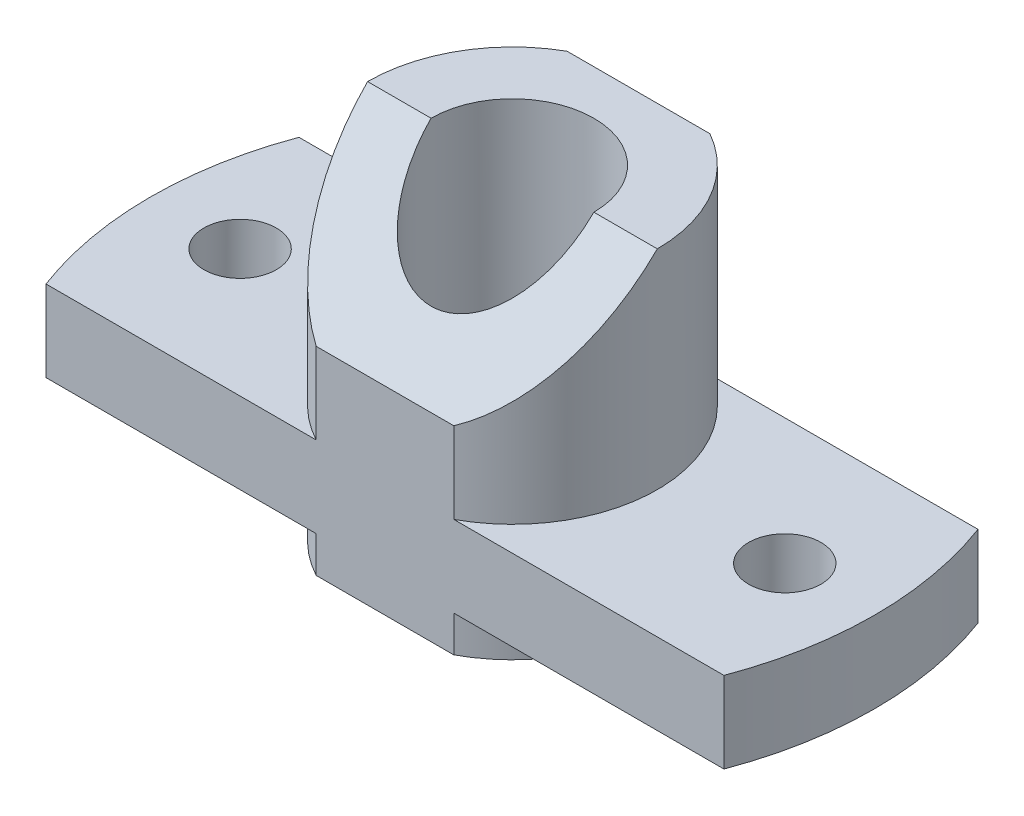
SolidWorks part; units mm, degrees
ref_plane "Front Plane" through (0, 0, 0) normal (0, 0, 1) x (1, 0, 0)
ref_plane "Top Plane" through (0, 0, 0) normal (0, 1, 0) x (1, 0, 0)
ref_plane "Right Plane" through (0, 0, 0) normal (1, 0, 0) x (0, 0, -1)
sketch "Sketch2" plane through (0, 0, 0) normal (0, 0, 1) x (1, 0, 0)
  line L0 (-63.5, 20.574) -> (-63.5, 6.35)
  line L1 (-63.5, 6.35) -> (-25.4, 6.35)
  line L2 (-25.4, 6.35) -> (-25.4, 0)
  line L3 (-25.4, 0) -> (0, 0)
  line L4 (0, 0) -> (0, 57.15)
  line L5 (0, 57.15) -> (-25.4, 57.15)
  line L6 (-25.4, 57.15) -> (-25.4, 20.574)
  line L7 (-25.4, 20.574) -> (-63.5, 20.574)
  line L8 (0, -55) -> (0, 55) construction
  line L9 (55, 0) -> (-55, 0) construction
  line L10 (0, 0) -> (0, 57.15) construction
  dimension "D1" = 38.1
  dimension "D2" = 14.224
  dimension "D3" = 25.4
  dimension "D4" = 6.35
  dimension "D5" = 57.15
revolve "Revolve1" add sketch "Sketch2" angle 360 about L10
sketch "Sketch3" plane through (0, 57.15, 0) normal (0, 1, 0) x (1, 0, 0)
  line L0 (-59.436, -22.352) -> (59.436, -22.352)
  line L1 (59.436, -22.352) -> (59.436, -63.5)
  line L2 (59.436, -63.5) -> (-59.436, -63.5)
  line L3 (-59.436, -63.5) -> (-59.436, -22.352)
  line L4 (-31.4325, 0) -> (31.4325, 0) construction
  circle A0 centre (0, 0) radius 63.5 construction
  dimension "D1" = 22.352
extrude "Cut-Extrude1" cut sketch "Sketch3" against normal through all
sketch "Sketch4" plane through (0, 57.15, 0) normal (0, 1, 0) x (1, 0, 0)
  line L0 (-59.5309, 22.098) -> (59.5309, 22.098)
  line L1 (59.5309, 22.098) -> (59.5309, 63.5)
  line L2 (59.5309, 63.5) -> (-59.5309, 63.5)
  line L3 (-59.5309, 63.5) -> (-59.5309, 22.098)
  line L4 (-31.4325, 0) -> (31.4325, 0) construction
  arc A0 (59.436, -22.352) -> (-59.436, -22.352) centre (0, 0) ccw construction
  dimension "D1" = 22.098
extrude "Cut-Extrude2" cut sketch "Sketch4" against normal through all
hole_wizard "1/2 (1.124) Dowel Hole1" positions "Sketch5" profile "Sketch6" hole size "1/2" standard "ANSI Inch" end condition through all
sketch "Sketch5" plane through (0, 57.15, 0) normal (0, 1, 0) x (1, 0, 0)
  point P0 (0, 0)
sketch "Sketch6" plane through (0, 57.15, 0) normal (1, 0, 0) x (0, 0, 1)
  line L0 (0, 0) -> (0, 57.15)
  line L1 (0, 57.15) -> (14.2748, 57.15)
  line L2 (14.2748, 57.15) -> (14.2748, 0)
  line L5 (14.2748, 0) -> (0, 0)
  line L11 (0, -6.35) -> (0, 107.95) construction
  dimension "Thru Hole Dia." = 28.5496
  dimension "Thru Hole Depth" = 57.15
hole_wizard "1/2 (0.5000) Dowel Hole1" positions "Sketch7" profile "Sketch8" hole size "1/2" standard "ANSI Inch" end condition through all
sketch "Sketch7" plane through (0, 20.574, 0) normal (0, 1, 0) x (1, 0, 0)
  line L0 (-31.4325, 0) -> (31.4325, 0) construction
  point P0 (-47.752, 0)
  point P4 (47.752, 0)
  point P12 (-73.0958, 51.9061)
  dimension "D1" = 47.752
  dimension "D2" = 95.504
sketch "Sketch8" plane through (-47.752, 20.574, 0) normal (1, 0, 0) x (0, 0, 1)
  line L0 (0, 0) -> (0, 20.574)
  line L1 (0, 20.574) -> (6.35, 20.574)
  line L2 (6.35, 20.574) -> (6.35, 0)
  line L5 (6.35, 0) -> (0, 0)
  line L11 (0, -6.35) -> (0, 107.95) construction
  dimension "Thru Hole Dia." = 12.7
  dimension "Thru Hole Depth" = 20.574
chamfer "Chamfer1" distance 22.352 angle 45 1 edges at (0, 57.15, 22.352)
